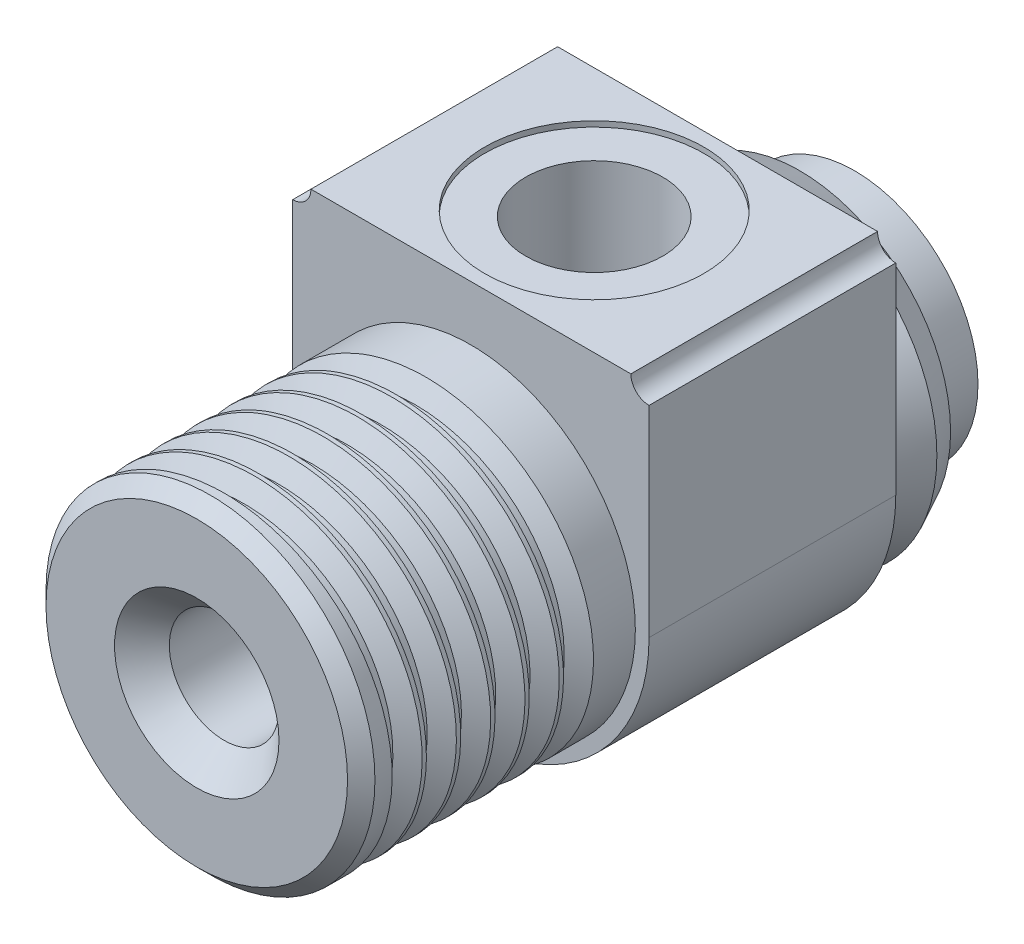
SolidWorks part; units mm, degrees
ref_plane "Front Plane" through (0, 0, 0) normal (0, 0, 1) x (1, 0, 0)
ref_plane "Top Plane" through (0, 0, 0) normal (0, 1, 0) x (1, 0, 0)
ref_plane "Right Plane" through (0, 0, 0) normal (1, 0, 0) x (0, 0, -1)
sketch "Sketch1" plane through (0, 0, 0) normal (0, 0, 1) x (1, 0, 0)
  circle A0 centre (0, 0) radius 5.5
  dimension "D1" = 11
ref_plane "Plane1" through (0, 0, 1) normal (0, 0, 1) x (1, 0, 0)
sketch "Sketch2" plane through (0, 0, 1) normal (0, 0, 1) x (1, 0, 0)
  circle A0 centre (0, 0) radius 6
  dimension "D1" = 12
ref_plane "Plane2" through (0, 0, 3) normal (0, 0, 1) x (1, 0, 0)
sketch "Sketch3" plane through (0, 0, 3) normal (0, 0, 1) x (1, 0, 0)
  circle A0 centre (0, 0) radius 5
  dimension "D1" = 10
loft "Loft1" add profiles "Sketch1", "Sketch2"
sketch "Sketch4" plane through (0, 0, 1) normal (0, 0, 1) x (1, 0, 0)
  circle A0 centre (0, 0) radius 6
loft "Loft3" add profiles "Sketch4", "Sketch3"
sketch "Sketch5" plane through (0, 0, 3) normal (0, 0, 1) x (1, 0, 0)
  circle A1 centre (0, 0) radius 6.5
  dimension "D1" = 13
extrude "Boss-Extrude1" add sketch "Sketch5" along normal blind 9
ref_plane "Plane3" through (0, 8, 0) normal (0, 1, 0) x (1, 0, 0)
sketch "Sketch6" plane through (0, 8, 0) normal (0, 1, 0) x (1, 0, 0)
  line L1 (-6.5, -3) -> (6.5, -3)
  line L2 (-6.5, -3) -> (-6.5, -12)
  line L3 (-6.5, -12) -> (6.5, -12)
  line L4 (6.5, -3) -> (6.5, -12)
extrude "Boss-Extrude2" add sketch "Sketch6" against normal up to surface (8 mm away) up to face at (6.5, 0, 12)
sketch "Sketch7" plane through (0, 0, 3) normal (0, 0, -1) x (-1, 0, 0)
  line L0 (-6.5, 8) -> (6.5, 8) construction
  line L1 (-6.5, 0) -> (-6.5, 8) construction
  line L2 (6.5, 0) -> (6.5, 8) construction
  line L3 (-6.5, 8) -> (-5.836, 8)
  line L4 (-6.5, 7.336) -> (-6.5, 8)
  line L5 (5.836, 8) -> (6.5, 8)
  line L6 (6.5, 7.336) -> (6.5, 8)
  arc A0 (-5.836, 8) -> (-6.5, 7.336) centre (-6.5, 8) cw
  arc A1 (6.5, 7.336) -> (5.836, 8) centre (6.5, 8) cw
extrude "Cut-Extrude1" cut sketch "Sketch7" against normal blind 9
sketch "Sketch8" plane through (0, 0, 12) normal (0, 0, 1) x (1, 0, 0)
  circle A0 centre (0, 0) radius 6
  dimension "D1" = 12
extrude "Boss-Extrude3" add sketch "Sketch8" along normal blind 10
sketch "Sketch15" plane through (0, 0, 22) normal (0, 0, 1) x (1, 0, 0)
  circle A0 centre (0, 0) radius 2
  dimension "D1" = 4
extrude "Cut-Extrude2" cut sketch "Sketch15" against normal through all
chamfer "Chamfer1" distance 1 angle 45 1 edges at (2, 0, 22)
sketch "Sketch16" plane through (0, 8, 0) normal (0, 1, 0) x (1, 0, 0)
  line L0 (5, -3) -> (-5, -3) construction
  circle A0 centre (0, -7.5) radius 4
  dimension "D1" = 8
  dimension "D2" = 4.5
extrude "Cut-Extrude4" cut sketch "Sketch16" against normal blind 0.2
sketch "Sketch17" plane through (0, 7.8, 0) normal (0, 1, 0) x (1, 0, 0)
  circle A0 centre (0, -7.5) radius 2.5
  dimension "D1" = 5
extrude "Cut-Extrude7" cut sketch "Sketch17" against normal blind 10
sketch "Sketch18" plane through (0, 0, 0) normal (0, 0, -1) x (-1, 0, 0)
  circle A0 centre (0, 0) radius 4.5
  dimension "D1" = 9
extrude "Boss-Extrude4" add sketch "Sketch18" along normal blind 2
sketch "Sketch19" plane through (0, 0, -2) normal (0, 0, -1) x (-1, 0, 0)
  circle A0 centre (0, 0) radius 2
  dimension "D1" = 4
extrude "Cut-Extrude8" cut sketch "Sketch19" against normal up to next
chamfer "Chamfer2" distance 0.5 angle 45 1 edges at (6, 0, 22)
thread "Thread1" pitch 1.25 start angle 0, offset 0, length 0, pitch 1.25, diameter 12
ref_plane "Plane4" through (-6, 0, 21.5) normal (0, -1, 0) x (-1, 0, 0)
sketch "Thread Profile1" plane through (-6, 0, 21.5) normal (0, -1, 0) x (-1, 0, 0)
  line L0 (0, 0) -> (0, 1.25) construction
  line L11 (0, 0) -> (0, 1.0937)
  line L12 (0, 1.0937) -> (-0.6766, 0.7031)
  line L13 (-0.6766, 0.7031) -> (-0.6766, 0.3906)
  line L15 (-0.6766, 0.3906) -> (0, 0)
  line L17 (-0.6766, 0.5469) -> (0, 0.5469) construction
  point P2 (0, 0)
  dimension "Pitch" = 1.25
  dimension "Profile_Angle" = 60
  dimension "Profile_Land" = 0.3125
  dimension "Profile_Height" = 0.6766
